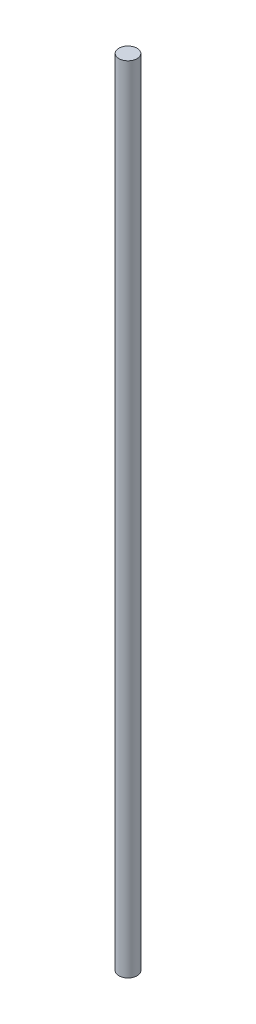
SolidWorks part; units mm, degrees
material "AISI 316 Annealed Stainless Steel Bar (SS)"
ref_plane "Front Plane" through (0, 0, 0) normal (0, 0, 1) x (1, 0, 0)
ref_plane "Top Plane" through (0, 0, 0) normal (0, 1, 0) x (1, 0, 0)
ref_plane "Right Plane" through (0, 0, 0) normal (1, 0, 0) x (0, 0, -1)
sketch "Sketch1" plane through (0, 0, 0) normal (0, 1, 0) x (1, 0, 0)
  circle A0 centre (0, 0) radius 4
  dimension "D1" = 8
extrude "Boss-Extrude1" add sketch "Sketch1" against normal blind 350
equation "\"rod_diameter\"= 8"
equation "\"rod_hole_thickness\"= 4"
equation "\"rod_radius\"= \"rod_diameter\" / 2"
equation "\"platter_diameter\"= 320"
equation "\"platter_radius\"= \"platter_diameter\" / 2"
equation "\"extruder_mount_hole_spacing\"= 90"
equation "\"arm_rod_spacing\"= 40"
equation "\"top_frame_rod_spacing\"= \"arm_rod_spacing\" + 40"
equation "\"motor_level_rod_spacing\"= 15"
equation "\"linear_bearing_diameter\"= 15"
equation "\"z_rod_spacing\"= 75"
equation "\"platter_rod_spacing\"= 50"
equation "\"rod_nut_thickness\"= 6.5"
equation "\"rod_nut_inscribed_diameter\"= 13"
equation "\"z_height\"= 350"
equation "\"D1@Sketch1\"= \"rod_diameter\""
equation "\"D1@Boss-Extrude1\"= \"z_height\""
